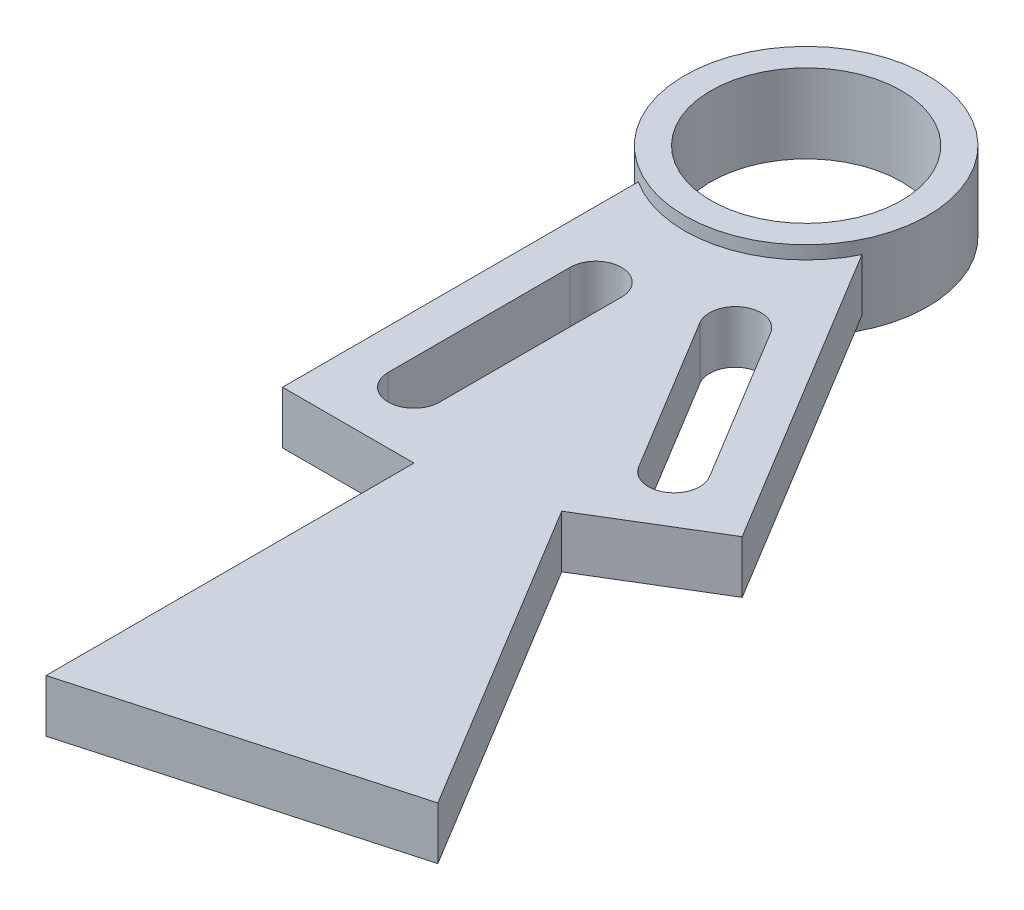
SolidWorks part; units mm, degrees
material "AISI 4130 Steel, annealed at 865C"
ref_plane "Front Plane" through (0, 0, 0) normal (0, 0, 1) x (1, 0, 0)
ref_plane "Top Plane" through (0, 0, 0) normal (0, 1, 0) x (1, 0, 0)
ref_plane "Right Plane" through (0, 0, 0) normal (1, 0, 0) x (0, 0, -1)
sketch "Sketch1" plane through (0, 0, 0) normal (0, 1, 0) x (1, 0, 0)
  line L0 (0, -50.4952) -> (0, -14.6812) construction
  line L1 (26.1781, -43.1795) -> (7.6111, -12.5542) construction
  line L2 (0, -47.3837) -> (0, -25.4127) construction
  line L5 (-3.1115, -47.3837) -> (-3.1115, -25.4127)
  line L8 (-7.9375, -55.3212) -> (7.9375, -55.3212)
  line L9 (21.8925, -51.4214) -> (35.4676, -43.1913)
  line L10 (-7.9375, -55.3212) -> (-7.9375, -12.3505)
  line L11 (35.4676, -43.1913) -> (13.1903, -6.4461)
  line L12 (7.9375, -55.3212) -> (7.9375, -99.7712)
  line L13 (21.8925, -51.4214) -> (44.9366, -89.4315)
  line L14 (7.9375, -99.7712) -> (44.9366, -89.4315)
  line L15 (0, -14.6812) -> (0, 0) construction
  line L16 (0, -55.3212) -> (0, -50.4952) construction
  line L17 (28.6801, -47.3063) -> (26.1781, -43.1795)
  line L18 (3.1115, -47.3837) -> (3.1115, -25.4127)
  line L19 (13.1747, -21.7309) -> (24.565, -40.5188) construction
  line L20 (15.8354, -20.1179) -> (27.2257, -38.9057)
  line L21 (10.5139, -23.344) -> (21.9043, -42.1319)
  line L22 (7.6111, -12.5542) -> (0, 0) construction
  line L23 (0, 0) -> (20.5089, -73.3882) construction
  line L25 (184.8058, -304.8281) -> (14.725, -24.2882) construction
  line L27 (0, 0) -> (26.4371, -94.6014) construction
  circle A0 centre (0, 0) radius 11.5062
  circle A1 centre (0, 0) radius 14.6812
  arc A2 (-3.1115, -47.3837) -> (3.1115, -47.3837) centre (0, -47.3837) ccw
  arc A3 (3.1115, -25.4127) -> (-3.1115, -25.4127) centre (0, -25.4127) ccw
  arc A4 (15.8354, -20.1179) -> (10.5139, -23.344) centre (13.1747, -21.7309) ccw
  arc A5 (21.9043, -42.1319) -> (27.2257, -38.9057) centre (24.565, -40.5188) ccw
  point P9 (0, -36.3982)
  point P14 (18.8698, -31.1249)
  point P23 (0, -55.3212)
  point P26 (28.6801, -47.3063)
  point P33 (0, -50.4952)
  point P36 (26.1781, -43.1795)
  point P38 (0, -22.3012)
  dimension "D2" = 29.3624
  dimension "D3" = 40.64
  dimension "D4" = 4.826
  dimension "D6" = 44.45
  dimension "D7" = 7.9375
  dimension "D5" = 4.826
  dimension "D8" = 7.62
  dimension "D9" = 76.2
extrude "Bearing extrude" add sketch "Sketch1" along normal mid plane 9.525 contours A1 A0 region at (-6.8368, 0, -12.521)
extrude "Boss-Extrude2" add sketch "Sketch1<5>" along normal mid plane 6.35 contours A1 L10 L8 L12 L14 L13 L9 L11 A4 A2 region at (15.6772, 0, 56.0987)
sketch "Sketch1<5>" plane through (0, 0, 0) normal (0, 1, 0) x (1, 0, 0) same geometry as "Sketch1"
sketch3d "Tab Point"
  line L0 (20.5089, 0, 73.3882) -> (20.5089, 22.225, 73.3882) construction
  line L1 (0, 0, 0) -> (20.5089, 0, 73.3882) construction
  line L2 (0, 0, 0) -> (26.4371, 0, 94.6014) construction
  dimension "D1" = 22.225
equation "\"Apex_thickness\"= .25"
equation "\"Bearing_diameter\"= .906"
equation "\"A-arm_angle\"= 32.91"
equation "\"D1@Sketch1\"=\"Bearing_diameter\""
equation "\"D1@Boss-Extrude2\"= \"Apex_thickness\""
equation "\"apex slot\"= 1.4"
equation "\"tube diameter\"= 5 / 8"
